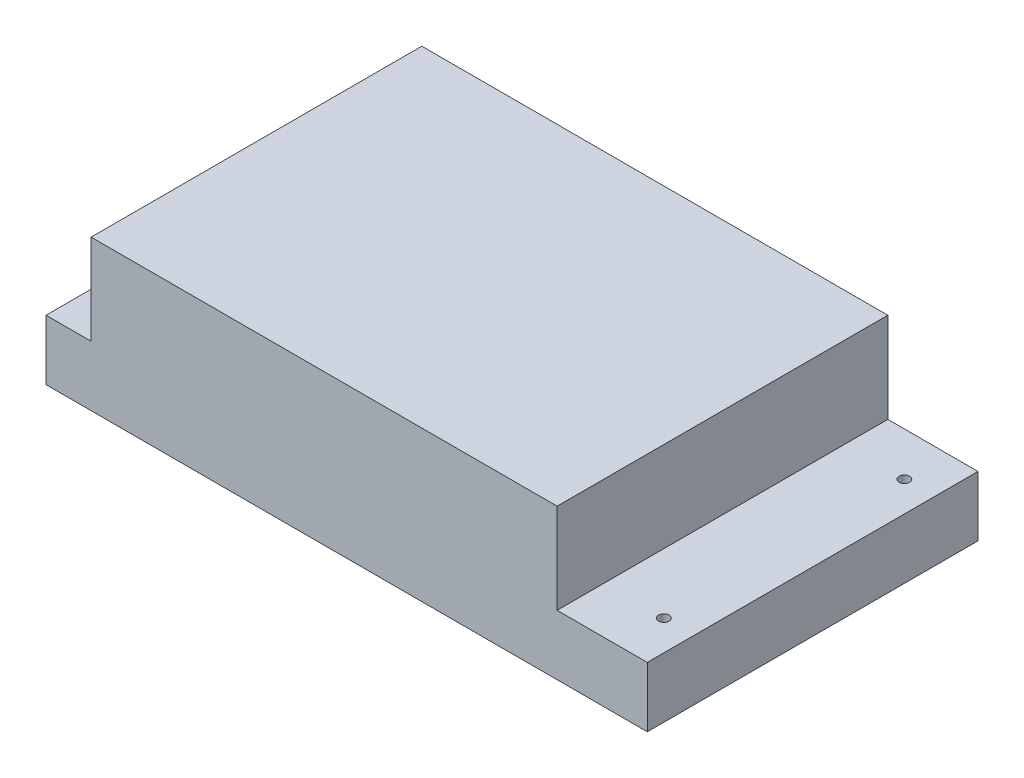
SolidWorks part; units mm, degrees
ref_plane "Front Plane" through (0, 0, 0) normal (0, 0, 1) x (1, 0, 0)
ref_plane "Top Plane" through (0, 0, 0) normal (0, 1, 0) x (1, 0, 0)
ref_plane "Right Plane" through (0, 0, 0) normal (1, 0, 0) x (0, 0, -1)
sketch "Sketch1" plane through (0, 0, 0) normal (0, 1, 0) x (1, 0, 0)
  line L1 (0, 0) -> (200, 0)
  line L2 (0, 0) -> (0, 110)
  line L3 (0, 110) -> (200, 110)
  line L4 (200, 0) -> (200, 110)
  dimension "D1" = 200
  dimension "D2" = 110
extrude "Boss-Extrude1" add sketch "Sketch1" along normal blind 50
sketch "Sketch2" plane through (0, 50, 0) normal (0, 1, 0) x (1, 0, 0)
  line L0 (0, 0) -> (200, 0) construction
  line L1 (200, 110) -> (170, 110)
  line L2 (200, 110) -> (200, 0)
  line L3 (200, 0) -> (170, 0)
  line L4 (170, 110) -> (170, 0)
  line L6 (0, 110) -> (15, 110)
  line L7 (0, 110) -> (0, 0)
  line L8 (0, 0) -> (15, 0)
  line L9 (15, 110) -> (15, 0)
  dimension "D1" = 30
  dimension "D2" = 15
extrude "Cut-Extrude1" cut sketch "Sketch2" against normal blind 30
sketch "Sketch3" plane through (0, 20, 0) normal (0, 1, 0) x (1, 0, 0)
  line L0 (200, 110) -> (170, 110) construction
  line L1 (200, 0) -> (200, 110) construction
  circle A0 centre (190, 95.5) radius 1.75
  circle A1 centre (190, 15.5) radius 1.75
  circle A2 centre (10, 95.5) radius 1.75
  circle A3 centre (10, 15.5) radius 1.75
  point P12 (0, 0)
  point P13 (0, 0)
  point P14 (5.5165, 15.5)
  dimension "D1" = 3.5
  dimension "D2" = 3.5
  dimension "D6" = 3.5
  dimension "D7" = 3.5
  dimension "D3" = 14.5
  dimension "D4" = 10
  dimension "D5" = 80
  dimension "D8" = 180
extrude "Cut-Extrude2" cut sketch "Sketch3" against normal blind 30
